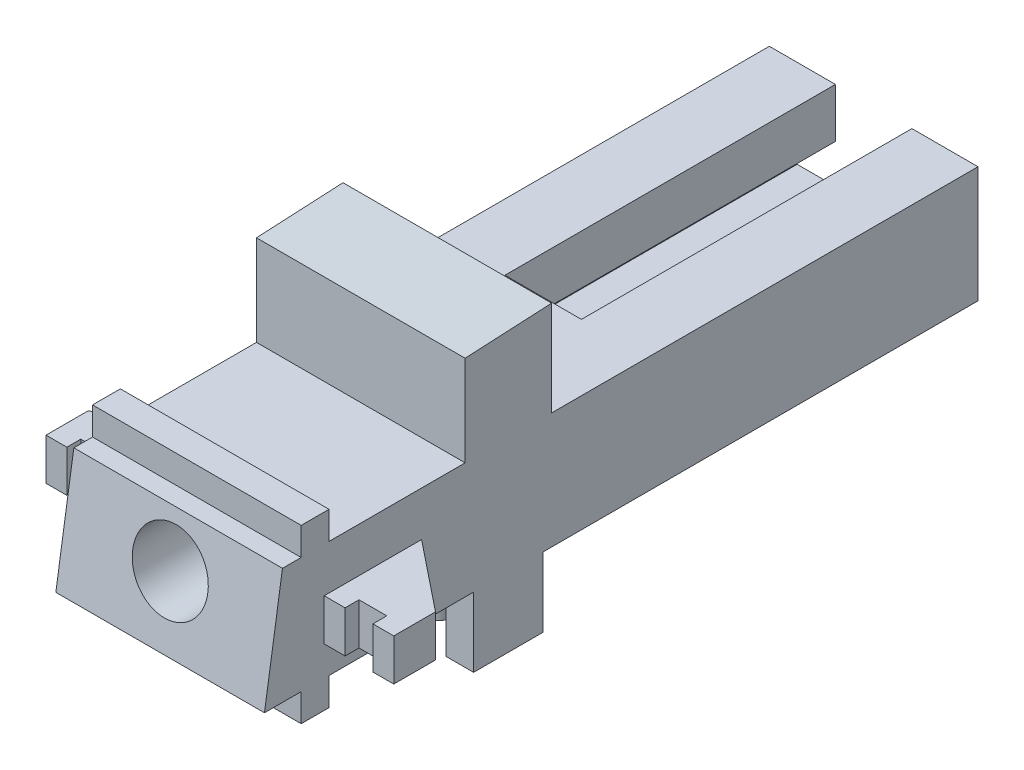
SolidWorks part; units mm, degrees
ref_plane "Front Plane" through (0, 0, 0) normal (0, 0, 1) x (1, 0, 0)
ref_plane "Top Plane" through (0, 0, 0) normal (0, 1, 0) x (1, 0, 0)
ref_plane "Right Plane" through (0, 0, 0) normal (1, 0, 0) x (0, 0, -1)
sketch "Sketch9" plane through (0, 0, 0) normal (0, 0, 1) x (1, 0, 0)
  line L1 (-7.5, 8.35) -> (7.5, 8.35)
  line L2 (-7.5, 8.35) -> (-7.5, 0)
  line L3 (-7.5, 0) -> (7.5, 0)
  line L4 (7.5, 8.35) -> (7.5, 0)
  line L5 (-7.5, 8.35) -> (7.5, 0) construction
  line L6 (-7.5, 0) -> (7.5, 8.35) construction
  point P0 (0, 4.175)
  point P19 (0, 0)
  dimension "D1" = 8.35
  dimension "D2" = 15
extrude "Boss-Extrude4" add sketch "Sketch9" along normal blind 50
sketch "Sketch7" plane through (0, 0, 0) normal (0, 0, 1) x (1, 0, 0)
  line L0 (-5.5, 2) -> (-5.5, 4.8)
  line L1 (-5.5, 4.8) -> (-2.75, 4.8)
  line L2 (-2.75, 4.8) -> (-2.75, 8.35)
  line L3 (-2.75, 8.35) -> (2.75, 8.35) construction
  line L4 (2.75, 8.35) -> (2.75, 4.8)
  line L5 (2.75, 4.8) -> (5.5, 4.8)
  line L6 (5.5, 4.8) -> (5.5, 2)
  line L7 (5.5, 2) -> (-5.5, 2)
  line L9 (7.5, 8.35) -> (-7.5, 8.35) construction
  line L11 (7.5, 0) -> (7.5, 8.35) construction
  line L13 (-2.75, 8.35) -> (2.75, 8.35)
  dimension "D1" = 2.8
  dimension "D2" = 2
  dimension "D3" = 11
  dimension "D4" = 5.5
  dimension "D5" = 2
extrude "Cut-Extrude4" cut sketch "Sketch7" along normal blind 23.76
sketch "Sketch21" plane through (-7.5, 0, 0) normal (-1, 0, 0) x (0, 0, 1)
  line L7 (50, 0) -> (51.2947, 0)
  line L8 (51.2947, 0) -> (50, 8.35)
  line L9 (50, 8.35) -> (50, 0)
extrude "Boss-Extrude9" add sketch "Sketch21" against normal up to surface (15 mm away) up to face at (7.5, 4.175, 25)
sketch "Sketch10" plane through (0, 0, 23.76) normal (0, 0, 1) x (1, 0, 0)
  line L0 (5.5, 2) -> (-5.5, 2) construction
  circle A0 centre (0, 4.7) radius 2.7
  dimension "D1" = 5.4
extrude "Cut-Extrude5" cut sketch "Sketch10" along normal up to surface (26.806 mm away) up to face at (0, 4.175, 50.6474)
sketch "Sketch12" plane through (7.5, 0, 0) normal (1, 0, 0) x (0, 0, -1)
  line L0 (-51.2947, 0) -> (0, 0) construction
  line L1 (-47, 5.14) -> (-44, 5.14)
  line L2 (-47, 5.14) -> (-47, 2.14)
  line L3 (-47, 2.14) -> (-44, 2.14)
  line L4 (-44, 5.14) -> (-44, 2.14)
  line L5 (-47, 5.14) -> (-44, 2.14) construction
  line L6 (-47, 2.14) -> (-44, 5.14) construction
  point P0 (-45.5, 3.64)
  dimension "D1" = 3
  dimension "D2" = 3
  dimension "D3" = 2.14
  dimension "D4" = 3
extrude "Boss-Extrude5" add sketch "Sketch12" along normal blind 5
ref_plane "Plane1" through (0, 0, 0) normal (1, 0, 0) x (0, 0, -1)
sketch "Sketch13" plane through (0, 0, 47) normal (0, 0, 1) x (1, 0, 0)
  line L1 (9, 5.14) -> (11, 5.14)
  line L2 (9, 5.14) -> (9, 2.14)
  line L3 (9, 2.14) -> (11, 2.14)
  line L4 (11, 5.14) -> (11, 2.14)
  line L6 (12.5, 5.14) -> (7.5, 5.14) construction
  line L7 (12.5, 2.14) -> (7.5, 2.14) construction
  point P8 (10, 5.14)
  point P9 (10, 5.14)
  dimension "D2" = 2
extrude "Cut-Extrude6" cut sketch "Sketch13" against normal blind 1
mirror "Mirror2" about plane through (0, 0, 0) normal (1, 0, 0) of "Boss-Extrude5"
mirror "Mirror4" about plane through (0, 0, 0) normal (1, 0, 0) of "Cut-Extrude6"
sketch "Sketch14" plane through (0, 5.14, 0) normal (0, 1, 0) x (1, 0, 0)
  line L0 (12.5, -44) -> (7.5, -40)
  line L1 (7.5, -50) -> (7.5, 0) construction
  line L2 (7.5, -40) -> (7.5, -44)
  line L3 (7.5, -44) -> (12.5, -44)
  dimension "D1" = 4
extrude "Boss-Extrude6" add sketch "Sketch14" against normal up to surface (3 mm away) up to face at (10, 2.14, 46)
mirror "Mirror5" about plane through (0, 0, 0) normal (1, 0, 0) of "Boss-Extrude6"
sketch "Sketch22" plane through (-7.5, 0, 0) normal (-1, 0, 0) x (0, 0, 1)
  line L0 (51.2947, 0) -> (0, 0) construction
  line L1 (48.6551, 0) -> (46.6551, 0)
  line L2 (48.6551, 0) -> (48.6551, -2)
  line L3 (48.6551, -2) -> (46.6551, -2)
  line L4 (46.6551, 0) -> (46.6551, -2)
  line L5 (48.6551, 0) -> (46.6551, -2) construction
  line L6 (48.6551, -2) -> (46.6551, 0) construction
  line L7 (50.6474, 4.175) -> (0, 4.175) construction
  line L8 (51.2947, 0) -> (50, 8.35) construction
  line L9 (0, 8.35) -> (0, 0) construction
  line L10 (48.6551, 10.35) -> (46.6551, 8.35) construction
  line L11 (48.6551, 8.35) -> (46.6551, 10.35) construction
  line L12 (46.6551, 8.35) -> (46.6551, 10.35)
  line L13 (48.6551, 10.35) -> (46.6551, 10.35)
  line L14 (48.6551, 8.35) -> (48.6551, 10.35)
  line L15 (48.6551, 8.35) -> (46.6551, 8.35)
  line L16 (50, 8.35) -> (0, 8.35) construction
  point P0 (47.6551, -1)
  point P18 (47.6551, 9.35)
  dimension "D1" = 2
extrude "Boss-Extrude10" add sketch "Sketch22" against normal up to surface (15 mm away) up to face at (7.5, 4.175, 25.3237)
sketch "Sketch23" plane through (0, 0, 0) normal (0, -1, 0) x (1, 0, 0)
  line L0 (-5.5, 23.76) -> (0, 23.76) construction
  line L2 (-7.5, 23.76) -> (7.5, 23.76) construction
  line L3 (7.5, 46.6551) -> (7.5, 0) construction
  line L4 (-7.5, 46.6551) -> (-7.5, 0) construction
  circle A0 centre (0, 29.26) radius 2.5
  dimension "D2" = 5
  dimension "D1" = 5.5
extrude "Cut-Extrude7" cut sketch "Sketch23" against normal up to surface (2 mm away) up to face at (2.7, 4.7, 23.76)
sketch "Sketch24" plane through (0, 0, 0) normal (0, -1, 0) x (1, 0, 0)
  line L0 (5.5, 36.26) -> (7.5, 36.26)
  line L1 (7.5, 46.6551) -> (7.5, 0) construction
  line L2 (7.5, 36.26) -> (7.5, 31.26)
  line L3 (7.5, 31.26) -> (5.5, 31.26)
  line L4 (5.5, 36.26) -> (-5.5, 36.26)
  line L5 (-5.5, 36.26) -> (-5.5, 31.26)
  line L6 (-5.5, 31.26) -> (5.5, 31.26)
  line L7 (5.5, 31.26) -> (5.5, 36.26)
  line L8 (5.5, 36.26) -> (-5.5, 36.26) construction
  line L9 (-5.5, 36.26) -> (-5.5, 31.26)
  line L10 (-5.5, 31.26) -> (5.5, 31.26) construction
  line L11 (5.5, 31.26) -> (5.5, 36.26)
  line L12 (-5.5, 36.26) -> (-7.5, 36.26)
  line L13 (-7.5, 46.6551) -> (-7.5, 0) construction
  line L14 (-7.5, 36.26) -> (-7.5, 31.26)
  line L15 (-7.5, 31.26) -> (-5.5, 31.26)
  line L24 (2.5, 34.76) -> (-2.5, 34.76) construction
  line L25 (2.5, 34.76) -> (-2.5, 34.76) construction
  line L26 (2.5, 32.76) -> (-2.5, 32.76) construction
  line L27 (2.5, 32.76) -> (-2.5, 32.76) construction
  line L28 (2.5, 33.01) -> (-2.5, 33.01)
  line L29 (2.5, 34.51) -> (-2.5, 34.51)
  line L34 (0, 0) -> (0, 51.2947) construction
  line L35 (-7.5, 0) -> (7.5, 0) construction
  line L36 (7.5, 51.2947) -> (-7.5, 51.2947) construction
  arc A0 (2.5, 32.76) -> (2.5, 34.76) centre (2.5, 33.76) ccw construction
  arc A1 (2.5, 32.76) -> (2.5, 34.76) centre (2.5, 33.76) ccw construction
  arc A2 (-2.5, 34.76) -> (-2.5, 32.76) centre (-2.5, 33.76) ccw construction
  arc A3 (-2.5, 34.76) -> (-2.5, 32.76) centre (-2.5, 33.76) ccw construction
  arc A4 (-2.5, 34.51) -> (-2.5, 33.01) centre (-2.5, 33.76) ccw
  arc A5 (2.5, 33.01) -> (2.5, 34.51) centre (2.5, 33.76) ccw
  dimension "D1" = 0
  dimension "D2" = 0.25
extrude "Boss-Extrude11" add sketch "Sketch24" along normal blind 5
sketch "Sketch25" plane through (7.5, 0, 0) normal (1, 0, 0) x (0, 0, -1)
  line L0 (-31.26, -5) -> (-36.26, -5) construction
  line L1 (-30.6504, 8.35) -> (-36.8696, 8.35)
  line L2 (-30.6504, 8.35) -> (-30.6504, 15.1816)
  line L4 (-36.8696, 8.35) -> (-36.8696, 14.8623)
  line L7 (-46.6551, 8.35) -> (0, 8.35) construction
  line L10 (-36.8696, 14.8623) -> (-30.6504, 15.1816)
  point P7 (-33.76, -5)
  point P8 (-33.76, 8.35)
extrude "Boss-Extrude12" add sketch "Sketch25" against normal up to surface (15 mm away) up to face at (-7.5, 2.5063, 38.5984)
